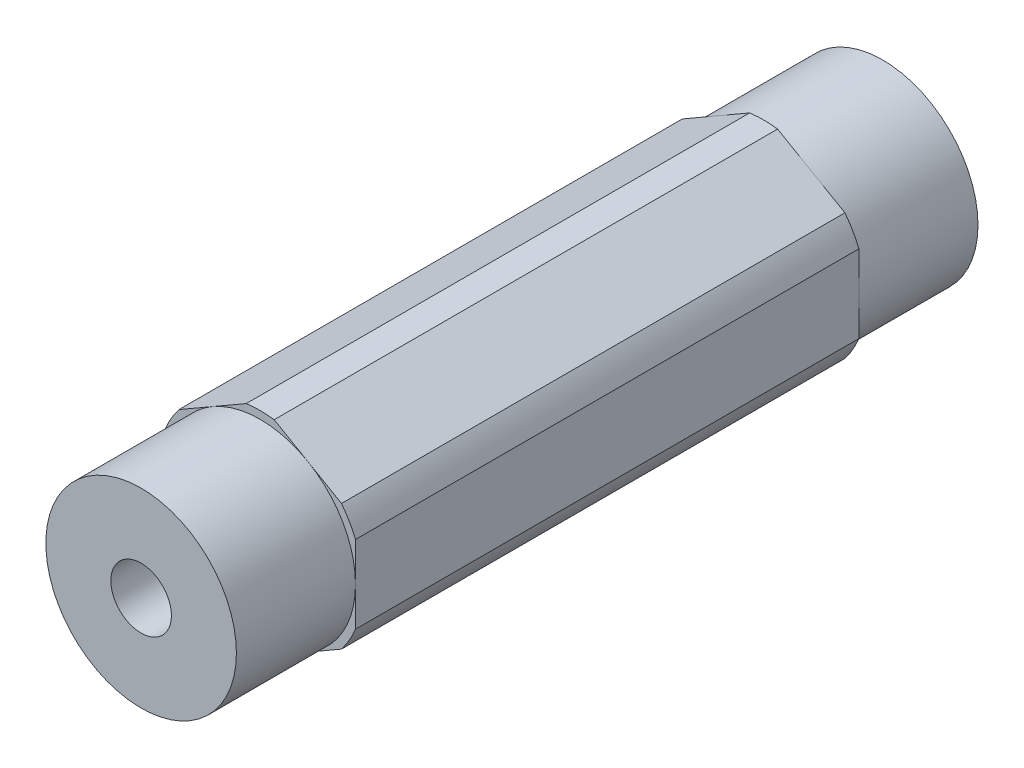
SolidWorks part; units mm, degrees
ref_plane "Front Plane" through (0, 0, 0) normal (0, 0, 1) x (1, 0, 0)
ref_plane "Top Plane" through (0, 0, 0) normal (0, 1, 0) x (1, 0, 0)
ref_plane "Right Plane" through (0, 0, 0) normal (1, 0, 0) x (0, 0, -1)
sketch "Sketch1" plane through (0, 0, 0) normal (0, 0, 1) x (1, 0, 0)
  line L1 (0, 7.3323) -> (-6.35, 3.6662)
  line L2 (-6.35, 3.6662) -> (-6.35, -3.6662)
  line L3 (-6.35, -3.6662) -> (0, -7.3323)
  line L4 (0, -7.3323) -> (6.35, -3.6662)
  line L5 (6.35, -3.6662) -> (6.35, 3.6662)
  line L6 (6.35, 3.6662) -> (0, 7.3323)
  circle A0 centre (0, 0) radius 6.35 construction
  circle A1 centre (0, 0) radius 6.858
  dimension "D1" = 12.7
  dimension "D2" = 13.716
extrude "Boss-Extrude1" add sketch "Sketch1" along normal mid plane 33.5509 contours L5 A1 L6 L1 L2 L3 L4 region at (0, 0, 0)
sketch "Sketch4" plane through (0, 0, 16.7754) normal (0, 0, 1) x (1, 0, 0)
  line L0 (5.4183, 4.2041) -> (0.9317, 6.7944) construction
  circle A0 centre (0, 0) radius 6.35
extrude "Boss-Extrude2" add sketch "Sketch4" along normal blind 7.9375
mirror "Mirror1" about plane through (0, 0, 0) normal (0, 0, 1) of "Boss-Extrude2"
hole_wizard "#10-32 Tapped Hole1" positions "3DSketch3" profile "Sketch7" tap size "#10-32" standard "ANSI Inch"
sketch3d "3DSketch3"
  line L0 (0, 0, 24.7129) -> (0, 0, 16.7754) construction
  line L1 (0, 0, -24.7129) -> (0, 0, -16.7754) construction
  point P0 (0, 0, 24.7129)
  point P4 (0, 0, -24.7129)
sketch "Sketch7" plane through (0, 0, 24.7129) normal (1, 0, 0) x (0, -1, 0)
  line L0 (0, 0) -> (0, 13.2428)
  line L1 (0, 13.2428) -> (2.0193, 12.0294)
  line L2 (2.0193, 12.0294) -> (2.0193, 0)
  line L5 (2.0193, 0) -> (0, 0)
  line L10 (0, 13.2428) -> (-2.0193, 12.0294) construction
  line L11 (0, -6.35) -> (0, 107.95) construction
  dimension "Tap Drill Dia." = 4.0386
  dimension "Tap Drill Depth" = 12.0294
  dimension "Drill Angle" = 118
cosmetic thread "Hole Thread1" parameters "D1"=9.652, "D2"=4.826
cosmetic thread "Hole Thread2" parameters "D1"=9.652, "D2"=4.826
